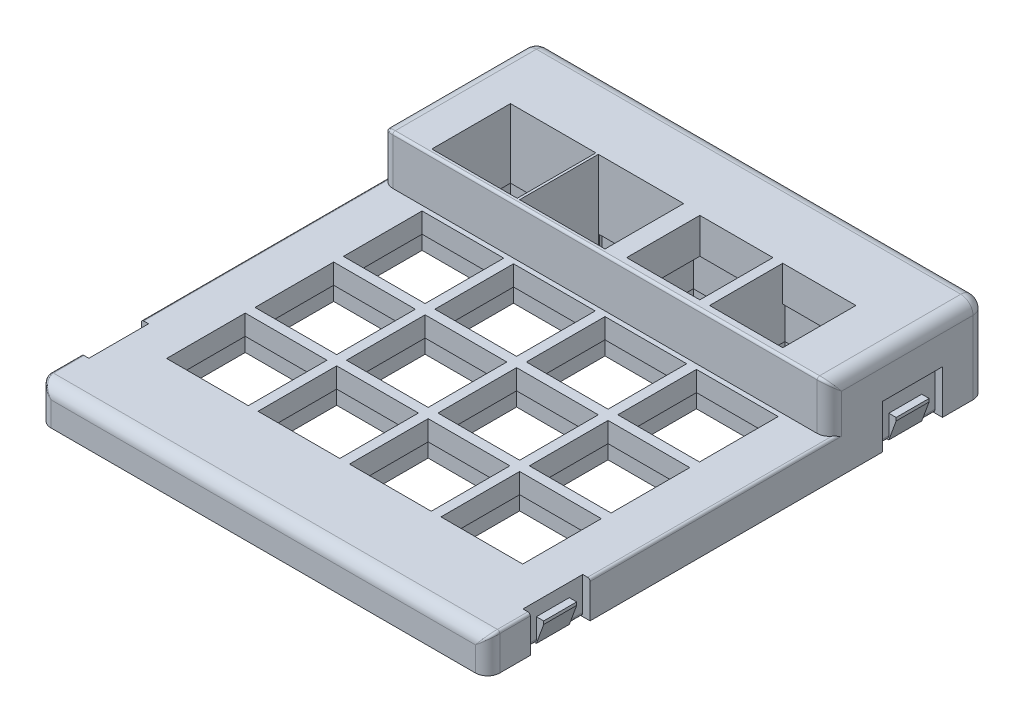
SolidWorks part; units mm, degrees
ref_plane "Ebene vorne" through (0, 0, 0) normal (0, 0, 1) x (1, 0, 0)
ref_plane "Ebene oben" through (0, 0, 0) normal (0, 1, 0) x (1, 0, 0)
ref_plane "Ebene rechts" through (0, 0, 0) normal (1, 0, 0) x (0, 0, -1)
ref_plane "Ebene1" through (0, 1.2, 0) normal (0, 1, 0) x (1, 0, 0)
sketch "Skizze2" plane through (0, 1.2, 0) normal (0, 1, 0) x (1, 0, 0)
  line L1 (-1.8, -1.8) -> (71.8, -1.8)
  line L2 (-1.8, -1.8) -> (-1.8, 79.8)
  line L3 (-1.8, 79.8) -> (71.8, 79.8)
  line L4 (71.8, -1.8) -> (71.8, 79.8)
  dimension "D1" = 79.8
  dimension "D2" = 1.8
  dimension "D3" = 71.8
  dimension "D4" = 1.8
extrude "Aufsatz-Linear austragen1" add sketch "Skizze2" along normal blind 6
surface "Oberfläche-Offset1" parameters "D1"=0
sketch "Skizze3" plane through (0, 1.2, 0) normal (0, 1, 0) x (1, 0, 0)
  line L1 (19.2, 11.55) -> (5.8, 11.55)
  line L2 (19.2, 11.55) -> (19.2, 24.45)
  line L3 (19.2, 24.45) -> (5.8, 24.45)
  line L4 (5.8, 11.55) -> (5.8, 24.45)
  line L6 (6.5, 24) -> (6.5, 12) construction
  line L7 (18.5, 12) -> (18.5, 24) construction
  line L8 (6.5, 12) -> (18.5, 12) construction
  line L10 (18.5, 24) -> (6.5, 24) construction
  dimension "D1" = 0.7
  dimension "D2" = 0.7
  dimension "D3" = 0.45
  dimension "D4" = 0.45
extrude "Schnitt-Linear austragen1" cut sketch "Skizze3" along normal through all
pattern_linear "Lineares Muster1" count 4 spacing 14.5 along (0, 0, -1) count 4 spacing 15 along (1, 0, 0) of "Schnitt-Linear austragen1"
sketch "Skizze4" plane through (0, 1.2, 0) normal (0, 1, 0) x (1, 0, 0)
  line L0 (19.2, 24.45) -> (5.8, 24.45) construction
  line L1 (19.6, 11.15) -> (5.4, 11.15)
  line L2 (19.6, 11.15) -> (19.6, 24.85)
  line L3 (19.6, 24.85) -> (5.4, 24.85)
  line L4 (5.4, 11.15) -> (5.4, 24.85)
  line L5 (19.2, 11.55) -> (19.2, 24.45) construction
  line L6 (5.8, 11.55) -> (19.2, 11.55) construction
  line L7 (5.8, 24.45) -> (5.8, 11.55) construction
  dimension "D1" = 0.4
  dimension "D2" = 0.4
  dimension "D3" = 0.4
  dimension "D4" = 0.4
extrude "Schnitt-Linear austragen2" cut sketch "Skizze4" along normal blind 2.7
pattern_linear "Lineares Muster2" count 4 spacing 14.5 along (0, 0, -1) count 4 spacing 15 along (1, 0, 0) of "Schnitt-Linear austragen2"
ref_plane "true_left" through (-1.8, 0, 0) normal (1, 0, 0) x (0, 0, -1)
ref_plane "Ebene4" through (0, 0, -39) normal (0, 0, 1) x (1, 0, 0)
sketch "Skizze6" plane through (-1.8, 0, 0) normal (1, 0, 0) x (0, 0, -1)
  line L0 (72.8, 7.2) -> (63, 7.2)
  line L1 (72.8, 1.2) -> (70.6, 1.2)
  line L4 (70.6, 1.2) -> (70.6, 5)
  line L7 (70.6, 5) -> (65.2, 5)
  line L10 (63, 7.2) -> (63, 1.2)
  line L11 (63, 1.2) -> (65.2, 1.2)
  line L12 (65.2, 5) -> (65.2, 1.2)
  line L13 (72.8, 7.2) -> (72.8, 1.2)
  line L14 (55, 1.2) -> (-55, 1.2) construction
  line L15 (39, 3.3) -> (39, -3.3) construction
  line L16 (5.2, 7.2) -> (15, 7.2)
  line L17 (15, 7.2) -> (15, 1.2)
  line L18 (15, 1.2) -> (12.8, 1.2)
  line L19 (12.8, 5) -> (12.8, 1.2)
  line L20 (7.4, 5) -> (12.8, 5)
  line L21 (7.4, 1.2) -> (7.4, 5)
  line L22 (5.2, 1.2) -> (7.4, 1.2)
  line L23 (5.2, 7.2) -> (5.2, 1.2)
  line L24 (0, 3.3) -> (0, -3.3) construction
  dimension "D1" = 2.2
  dimension "D2" = 2.2
  dimension "D3" = 6
  dimension "D4" = 63
  dimension "D5" = 5.4
extrude "Schnitt-Linear austragen6" cut sketch "Skizze6" along normal blind 1.2
ref_plane "Ebene5" through (35, 0, 0) normal (1, 0, 0) x (0, 0, -1)
mirror "Spiegeln1" about plane through (35, 0, 0) normal (1, 0, 0) of "Schnitt-Linear austragen6"
fillet "Verrundung1" radius 0.6 8 edges at (70.6, 1.2, -71.7) (70.6, 1.2, -64.1) (70.6, 1.2, -13.9) (70.6, 1.2, -6.3) (-0.6, 1.2, -13.9) (-0.6, 1.2, -6.3) (-0.6, 1.2, -71.7) (-0.6, 1.2, -64.1)
chamfer "Fase1" distance 1.2 angle 70 4 edges at (71.8, 1.2, -67.9) (71.8, 1.2, -10.1) (-1.8, 1.2, -10.1) (-1.8, 1.2, -67.9)
ref_plane "Ebene6" through (0, 7.2, 0) normal (0, 1, 0) x (1, 0, 0)
sketch "Skizze7" plane through (0, 7.2, 0) normal (0, 1, 0) x (1, 0, 0)
  line L1 (-1.8, 54.25) -> (71.8, 54.25)
  line L2 (-1.8, 54.25) -> (-1.8, 79.8)
  line L3 (-1.8, 79.8) -> (71.8, 79.8)
  line L4 (71.8, 54.25) -> (71.8, 79.8)
  line L5 (0, -3.3) -> (0, 3.3) construction
  line L6 (-3.3, 0) -> (3.3, 0) construction
  line L7 (34.2, 55.05) -> (20.2, 55.05)
  line L8 (5.8, 55.05) -> (19.8, 55.05)
  line L9 (5.8, 55.05) -> (5.8, 67.95)
  line L10 (5.8, 67.95) -> (19.8, 67.95)
  line L11 (19.8, 55.05) -> (19.8, 67.95)
  line L12 (34.2, 55.05) -> (34.2, 67.95)
  line L13 (34.2, 67.95) -> (20.2, 67.95)
  line L14 (20.2, 55.05) -> (20.2, 67.95)
  line L15 (37.2, 55.6) -> (49.2, 55.6)
  line L16 (37.2, 55.6) -> (37.2, 67.6)
  line L17 (37.2, 67.6) -> (49.2, 67.6)
  line L18 (49.2, 55.6) -> (49.2, 67.6)
  line L19 (50.8, 55.6) -> (62.8, 55.6)
  line L20 (50.8, 55.6) -> (50.8, 67.6)
  line L21 (50.8, 67.6) -> (62.8, 67.6)
  line L22 (62.8, 55.6) -> (62.8, 67.6)
  dimension "D1" = 1.8
  dimension "D2" = 73.6
  dimension "D3" = 79.8
  dimension "D4" = 54.25
  dimension "D5" = 67.95
  dimension "D6" = 5.8
  dimension "D7" = 55.05
  dimension "D8" = 14
  dimension "D9" = 0.4
  dimension "D10" = 14
  dimension "D11" = 12
  dimension "D12" = 12
  dimension "D13" = 1.6
  dimension "D14" = 55.6
  dimension "D15" = 49.2
extrude "Aufsatz-Linear austragen2" add sketch "Skizze7" along normal blind 8
sketch "Skizze8" plane through (0, 7.2, 0) normal (0, 1, 0) x (1, 0, 0)
  line L1 (5.8, 55.05) -> (19.8, 55.05)
  line L2 (5.8, 55.05) -> (5.8, 67.95)
  line L3 (5.8, 67.95) -> (19.8, 67.95)
  line L4 (19.8, 55.05) -> (19.8, 67.95)
  line L5 (20.2, 67.95) -> (34.2, 67.95)
  line L6 (20.2, 67.95) -> (20.2, 55.05)
  line L7 (20.2, 55.05) -> (34.2, 55.05)
  line L8 (34.2, 67.95) -> (34.2, 55.05)
  dimension "D1" = 14
  dimension "D3" = 55.05
  dimension "D4" = 0.4
  dimension "D5" = 5.8
  dimension "D6" = 67.95
extrude "Schnitt-Linear austragen8" cut sketch "Skizze8" against normal blind 8
chamfer "Fase2" distance 1.2 angle 45 2 edges at (-1.8, 7.2, -67.9) (71.8, 7.2, -67.9)
sketch "Skizze9" plane through (0, 7.2, 0) normal (0, 1, 0) x (1, 0, 0)
  line L0 (64.2, 67.95) -> (50.8, 67.95) construction
  line L1 (64.2, 55.05) -> (50.8, 55.05)
  line L2 (64.2, 55.05) -> (64.2, 67.95)
  line L3 (64.2, 67.95) -> (50.8, 67.95)
  line L4 (50.8, 55.05) -> (50.8, 67.95)
  line L5 (49.2, 55.05) -> (35.8, 55.05)
  line L6 (49.2, 55.05) -> (49.2, 67.95)
  line L7 (49.2, 67.95) -> (35.8, 67.95)
  line L8 (35.8, 55.05) -> (35.8, 67.95)
  line L9 (64.2, 55.05) -> (64.2, 67.95) construction
  line L10 (50.8, 55.05) -> (64.2, 55.05) construction
  line L11 (20.4, 55.05) -> (34.2, 55.05) construction
  line L12 (35.8, 55.05) -> (49.2, 55.05) construction
  line L13 (35.8, 55.05) -> (49.2, 55.05) construction
  line L14 (35.8, 67.95) -> (35.8, 55.05) construction
  dimension "D1" = 1.6
extrude "Schnitt-Linear austragen9" cut sketch "Skizze9" along normal blind 2.2
fillet "Verrundung2" radius 2 10 edges at (35, 7.2, 1.8) (-1.8, 8.2, -79.8) (71.8, 8.2, -79.8) (71.8, 4.2, 1.8) (-1.8, 4.2, 1.8) (-1.8, 15.2, -67.025) (71.8, 15.2, -67.025) (35, 15.2, -79.8) (-1.8, 11.2, -54.25) (71.8, 11.2, -54.25)
fillet "Verrundung3" radius 0.4 7 edges at (-1.2142, 14.6142, -54.8358) (71.2142, 14.6142, -54.8358) (35, 15.2, -54.25) (-1.2142, 6.6142, 1.2142) (71.2142, 6.6142, 1.2142) (-1.8, 7.2, -2.7) (71.8, 7.2, -2.7)
